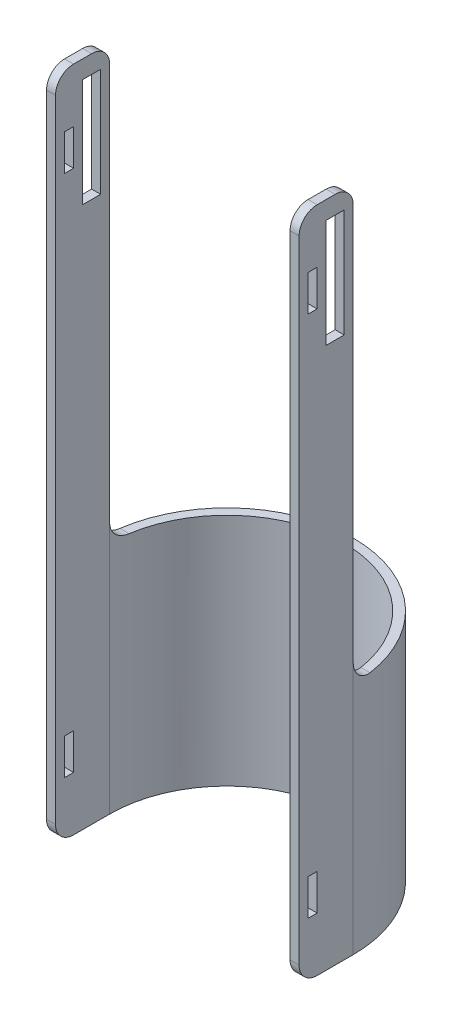
SolidWorks part; units mm, degrees
material "PE High Density"
ref_plane "Front Plane" through (0, 0, 0) normal (0, 0, 1) x (1, 0, 0)
ref_plane "Top Plane" through (0, 0, 0) normal (0, 1, 0) x (1, 0, 0)
ref_plane "Right Plane" through (0, 0, 0) normal (1, 0, 0) x (0, 0, -1)
sketch "Sketch1" plane through (0, 0, 0) normal (0, 1, 0) x (1, 0, 0)
  line L0 (-70, 0) -> (70, 0) construction
  line L1 (-65, 0) -> (-70, 0)
  line L2 (70, 0) -> (65, 0)
  arc A0 (70, 0) -> (-70, 0) centre (0, 0) ccw
  arc A1 (65, 0) -> (-65, 0) centre (0, 0) ccw
  dimension "D1" = 65
  dimension "D2" = 70
extrude "Boss-Extrude1" add sketch "Sketch1" along normal blind 130
sketch "Sketch2" plane through (0, 0, 0) normal (0, 0, 1) x (1, 0, 0)
  line L1 (65, 130) -> (70, 130)
  line L2 (65, 130) -> (65, 0)
  line L3 (65, 0) -> (70, 0)
  line L4 (70, 130) -> (70, 0)
  line L5 (-70, 130) -> (-65, 130)
  line L6 (-70, 130) -> (-70, 0)
  line L7 (-70, 0) -> (-65, 0)
  line L8 (-65, 130) -> (-65, 0)
extrude "Boss-Extrude2" add sketch "Sketch2" along normal blind 30
sketch "Sketch3" plane through (0, 130, 0) normal (0, 1, 0) x (1, 0, 0)
  line L1 (-65, -30) -> (-70, -30)
  line L2 (-65, -30) -> (-65, 0)
  line L3 (-65, 0) -> (-70, 0)
  line L4 (-70, -30) -> (-70, 0)
  line L5 (70, -30) -> (65, -30)
  line L6 (70, -30) -> (70, 0)
  line L7 (70, 0) -> (65, 0)
  line L8 (65, -30) -> (65, 0)
extrude "Boss-Extrude3" add sketch "Sketch3" along normal blind 240
sketch "Sketch5" plane through (-70, 0, 0) normal (-1, 0, 0) x (0, 0, 1)
  line L0 (0, 370) -> (30, 370) construction
  line L1 (5, 360) -> (15, 360)
  line L2 (5, 360) -> (5, 300)
  line L3 (5, 300) -> (15, 300)
  line L4 (15, 360) -> (15, 300)
  line L5 (0, 370) -> (0, 130) construction
  dimension "D1" = 60
  dimension "D2" = 10
  dimension "D3" = 10
  dimension "D4" = 5
extrude "Cut-Extrude1" cut sketch "Sketch5" against normal blind 240
sketch "Sketch6" plane through (-70, 0, 0) normal (-1, 0, 0) x (0, 0, 1)
  line L0 (17.5605, 360) -> (17.5605, 300) construction
  line L1 (20, 340) -> (25, 340)
  line L2 (20, 340) -> (20, 320)
  line L3 (20, 320) -> (25, 320)
  line L4 (25, 340) -> (25, 320)
  line L5 (15, 360) -> (5, 360) construction
  line L7 (15, 300) -> (15, 360) construction
  dimension "D1" = 20
  dimension "D2" = 5
  dimension "D3" = 20
  dimension "D4" = 5
extrude "Cut-Extrude2" cut sketch "Sketch6" against normal through all
fillet "Fillet1" radius 10 4 edges at (67.5, 370, 30) (-67.5, 370, 30) (-67.5, 370, 0) (67.5, 370, 0)
fillet "Fillet2" radius 10 2 edges at (67.5, 0, 30) (-67.5, 0, 30)
fillet "Fillet3" radius 10 2 edges at (67.5, 130, 0) (-67.5, 130, 0)
sketch "Sketch8" plane through (-70, 0, 0) normal (-1, 0, 0) x (0, 0, 1)
  line L1 (20, 50) -> (25, 50)
  line L2 (20, 50) -> (20, 30)
  line L3 (20, 30) -> (25, 30)
  line L4 (25, 50) -> (25, 30)
  line L5 (20, 0) -> (0, 0) construction
  line L6 (30, 360) -> (30, 10) construction
  dimension "D1" = 20
  dimension "D2" = 5
  dimension "D3" = 30
  dimension "D4" = 5
extrude "Cut-Extrude3" cut sketch "Sketch8" against normal through all
ref_plane "Plane1" through (0, 65, 0) normal (0, 1, 0) x (1, 0, 0)
sketch "Sketch9" plane through (0, 65, 0) normal (0, 1, 0) x (1, 0, 0)
  line L0 (-21.6312, 66.574) -> (-21.6312, 76.574)
  line L1 (-21.6312, 76.574) -> (21.6312, 76.574)
  line L2 (21.6312, 76.574) -> (21.6312, 66.574)
  line L3 (-70, 0) -> (70, 0)
  line L4 (0, 0) -> (-21.6312, 66.574) construction
  line L5 (0, 0) -> (21.6312, 66.574) construction
  arc A0 (69.282, 10) -> (-69.282, 10) centre (0, 0) ccw construction
  arc A1 (70, 0) -> (-21.6312, 66.574) centre (0, 0) ccw
  point P13 (0, 0)
  dimension "D1" = 72
  dimension "D2" = 72
  dimension "D3" = 10
  dimension "D4" = 10
extrude "Boss-Extrude4" add sketch "Sketch9" along normal mid plane 60 contours A1 L2 L1 L0 region at (0, 65, -72.6545)
fillet "Fillet4" radius 5 4 edges at (0, 35, -76.574) (21.6312, 65, -76.574) (-21.6312, 65, -76.574) (0, 95, -76.574)
sketch "Sketch10" plane through (0, 0, -76.574) normal (0, 0, -1) x (-1, 0, 0)
  line L0 (16.6312, 90) -> (-16.6312, 90) construction
  line L1 (-16.6312, 90) -> (-16.6312, 40) construction
  line L2 (16.6312, 40) -> (16.6312, 90) construction
  line L3 (16.6312, 90) -> (-16.6312, 90) construction
  line L4 (-16.6312, 40) -> (16.6312, 40) construction
  line L5 (-16.6312, 40) -> (16.6312, 40) construction
  circle A0 centre (-11.6312, 85) radius 1.0922
  circle A1 centre (11.6312, 85) radius 1.0922
  circle A2 centre (-11.6312, 45) radius 1.0922
  circle A3 centre (11.6312, 45) radius 1.0922
  dimension "D1" = 2.1844
  dimension "D2" = 2.1844
  dimension "D3" = 2.1844
  dimension "D4" = 2.1844
  dimension "D5" = 5
  dimension "D7" = 5
  dimension "D8" = 5
  dimension "D9" = 5
  dimension "D10" = 5
  dimension "D11" = 5
  dimension "D12" = 5
  dimension "D6" = 5
extrude "Cut-Extrude4" cut sketch "Sketch10" against normal blind 5
cosmetic thread "Cosmetic Thread6" parameters "D2"=3.1844
cosmetic thread "Cosmetic Thread7" parameters "D2"=3.1844
cosmetic thread "Cosmetic Thread8" parameters "D2"=3.1844
cosmetic thread "Cosmetic Thread9" parameters "D2"=3.1844
